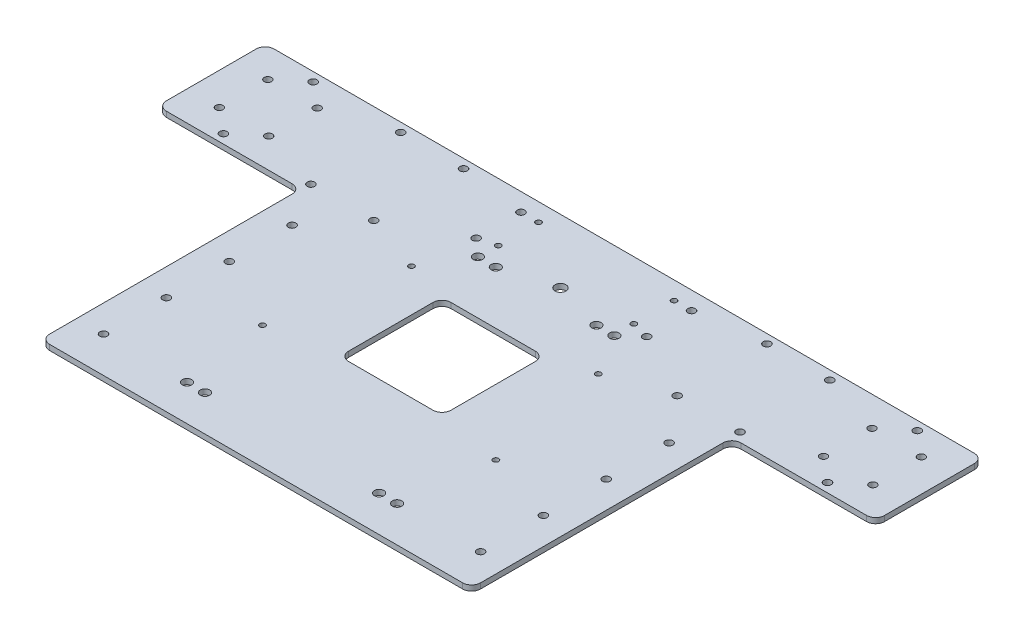
SolidWorks part; units mm, degrees
material "Thornel Mat VMA"
ref_plane "前视基准面" through (0, 0, 0) normal (0, 0, 1) x (1, 0, 0)
ref_plane "上视基准面" through (0, 0, 0) normal (0, 1, 0) x (1, 0, 0)
ref_plane "右视基准面" through (0, 0, 0) normal (1, 0, 0) x (0, 0, -1)
sketch "草图1" plane through (0, 0, 0) normal (0, 1, 0) x (1, 0, 0)
  line L0 (35.5759, -158.8718) -> (35.5759, 46.1282) construction
  line L1 (-164.4241, -13.8718) -> (235.5759, -13.8718)
  line L2 (-164.4241, -13.8718) -> (-164.4241, 46.1282)
  line L3 (-164.4241, 46.1282) -> (235.5759, 46.1282)
  line L4 (235.5759, -13.8718) -> (235.5759, 46.1282)
  line L5 (-11.9241, 36.1282) -> (83.0759, 36.1282) construction
  line L6 (-11.9241, 11.1282) -> (83.0759, 11.1282) construction
  line L7 (-84.4241, -158.8718) -> (155.5759, -158.8718)
  line L8 (-84.4241, -158.8718) -> (-84.4241, -13.8718)
  line L9 (-84.4241, -13.8718) -> (155.5759, -13.8718)
  line L10 (155.5759, -158.8718) -> (155.5759, -13.8718)
  line L11 (25.0759, 10.6282) -> (46.0759, 10.6282) construction
  line L12 (25.0759, 0.1282) -> (46.0759, 0.1282) construction
  line L13 (25.0759, 0.1282) -> (25.0759, 21.1282) construction
  line L14 (25.0759, 21.1282) -> (46.0759, 21.1282) construction
  line L15 (46.0759, 0.1282) -> (46.0759, 21.1282) construction
  line L16 (7.0759, -55.3718) -> (64.0759, -55.3718) construction
  line L17 (7.0759, -26.8718) -> (64.0759, -26.8718)
  line L18 (7.0759, -26.8718) -> (7.0759, -83.8718)
  line L19 (7.0759, -83.8718) -> (64.0759, -83.8718)
  line L20 (64.0759, -26.8718) -> (64.0759, -83.8718)
  line L21 (35.5759, 21.1282) -> (35.5759, 0.1282) construction
  circle A0 centre (-11.9241, 36.1282) radius 2.1
  circle A1 centre (-11.9241, 11.1282) radius 2.1
  circle A2 centre (83.0759, 11.1282) radius 2.1
  circle A3 centre (83.0759, 36.1282) radius 2.1
  circle A8 centre (35.5759, 10.6282) radius 3.05
  point P0 (0, 0)
  point P6 (0, -121.2547)
  point P16 (35.5759, 36.1282)
  point P19 (35.5759, 11.1282)
  point P23 (35.5759, 5.0732)
  point P30 (35.5759, -28.1434)
  point P35 (35.5759, -26.8718)
  dimension "D8" = 21
  dimension "D13" = 6.1
  dimension "D14" = 10.5
  dimension "D15" = 4.2
  dimension "D1" = 400
  dimension "D2" = 60
  dimension "D3" = 145
  dimension "D4" = 240
  dimension "D5" = 10
  dimension "D6" = 95
  dimension "D7" = 25
  dimension "D9" = 189.5
  dimension "D10" = 27
  dimension "D11" = 15
  dimension "D12" = 57
extrude "构型与裁判孔" add sketch "草图1" along normal blind 3 contours L1 L4 L3 L2 A3 L15 L12 L13 L14 A0 A1 A2 | L7 L10 L1 L8 region at (35.5759, 0, -16.1176) region at (35.5759, 0, 89.564)
sketch "草图2" plane through (0, 3, 0) normal (0, 1, 0) x (1, 0, 0)
  line L0 (-164.4241, 16.1282) -> (235.5759, 16.1282) construction
  line L1 (-164.4241, -13.8718) -> (-164.4241, 46.1282) construction
  line L2 (235.5759, -13.8718) -> (235.5759, 46.1282) construction
  line L3 (35.5759, 46.1282) -> (35.5759, -158.8718) construction
  line L4 (-164.4241, 46.1282) -> (235.5759, 46.1282) construction
  line L5 (-84.4241, -158.8718) -> (155.5759, -158.8718) construction
  line L6 (-146.4241, 2.6282) -> (-146.4241, 29.6282) construction
  line L7 (-118.9241, 2.6282) -> (-118.9241, 29.6282) construction
  line L8 (-146.4241, 29.6282) -> (-118.9241, 29.6282) construction
  line L9 (-48.9241, -8.8718) -> (-48.9241, 41.1282) construction
  line L10 (-132.6741, 29.6282) -> (-132.6741, 46.1282) construction
  line L11 (-132.6741, 41.1282) -> (-83.9241, 41.1282) construction
  circle A0 centre (-146.4241, 29.6282) radius 2.05
  circle A1 centre (-146.4241, 2.6282) radius 2.05
  circle A2 centre (-118.9241, 29.6282) radius 2.05
  circle A3 centre (-118.9241, 2.6282) radius 2.05
  circle A4 centre (-48.9241, 41.1282) radius 2.1
  circle A5 centre (-83.9241, 41.1282) radius 2.1
  circle A6 centre (-48.9241, -8.8718) radius 2.1
  circle A7 centre (-83.9241, -8.8718) radius 2.1
  circle A8 centre (-132.6741, 41.1282) radius 2.1
  circle A9 centre (-132.6741, -8.8718) radius 2.1
  circle A10 centre (203.8259, -8.8718) radius 2.1
  circle A11 centre (203.8259, 41.1282) radius 2.1
  circle A12 centre (155.0759, -8.8718) radius 2.1
  circle A13 centre (120.0759, -8.8718) radius 2.1
  circle A14 centre (155.0759, 41.1282) radius 2.1
  circle A15 centre (120.0759, 41.1282) radius 2.1
  circle A16 centre (190.0759, 2.6282) radius 2.05
  circle A17 centre (190.0759, 29.6282) radius 2.05
  circle A18 centre (217.5759, 2.6282) radius 2.05
  circle A19 centre (217.5759, 29.6282) radius 2.05
  point P15 (-146.4241, 16.1282)
  point P20 (-118.9241, 16.1282)
  point P25 (-48.9241, 16.1282)
  dimension "D2" = 4.1
  dimension "D4" = 5
  dimension "D5" = 4.2
  dimension "D7" = 2
  dimension "D8" = 18
  dimension "D1" = 27
  dimension "D3" = 45.5
  dimension "D6" = 70
extrude "切除-拉伸1" cut sketch "草图2" against normal through all
fillet "圆角1" radius 5 12 edges at (155.5759, 1.5, 13.8718) (-84.4241, 1.5, 13.8718) (235.5759, 1.5, -46.1282) (235.5759, 1.5, 13.8718) (155.5759, 1.5, 158.8718) (-84.4241, 1.5, 158.8718) (-164.4241, 1.5, -46.1282) (-164.4241, 1.5, 13.8718) (7.0759, 1.5, 83.8718) (64.0759, 1.5, 83.8718) (64.0759, 1.5, 26.8718) (7.0759, 1.5, 26.8718)
sketch "草图3" plane through (0, 3, 0) normal (0, 1, 0) x (1, 0, 0)
  line L0 (-89.4241, -13.8718) -> (160.5759, -13.8718) construction
  line L1 (-69.4241, -13.8718) -> (-69.4241, -158.8718) construction
  line L2 (-79.4241, -158.8718) -> (150.5759, -158.8718) construction
  line L3 (35.5759, 46.1282) -> (35.5759, -158.8718) construction
  line L4 (-159.4241, 46.1282) -> (230.5759, 46.1282) construction
  line L5 (-84.4241, -153.8718) -> (-84.4241, -18.8718) construction
  line L6 (7.0759, -55.3718) -> (64.0759, -55.3718) construction
  line L7 (190.0759, 2.6282) -> (-118.9241, 2.6282) construction
  line L8 (-16.4241, -20.3718) -> (-29.4241, -20.3718) construction
  line L9 (-48.9617, -13.8718) -> (-48.9617, -158.8718) construction
  line L10 (-79.4241, -158.8718) -> (150.5759, -158.8718) construction
  line L11 (-84.4241, -153.8718) -> (-84.4241, -18.8718) construction
  line L12 (-16.4241, -20.3718) -> (-16.4241, -90.3718) construction
  line L13 (-16.4241, -90.3718) -> (-29.4241, -90.3718) construction
  line L14 (-29.4241, -20.3718) -> (-29.4241, -90.3718) construction
  line L15 (-22.9241, -90.3718) -> (-22.9241, -20.3718) construction
  line L16 (-16.4241, -55.3718) -> (-29.4241, -55.3718) construction
  line L17 (7.0759, -31.8718) -> (7.0759, -78.8718) construction
  line L18 (-69.4241, -138.8718) -> (140.5759, -138.8718) construction
  circle A0 centre (-69.4241, -33.8718) radius 2.1
  circle A1 centre (-69.4241, -68.8718) radius 2.1
  circle A2 centre (-69.4241, -103.8718) radius 2.1
  circle A3 centre (-69.4241, -138.8718) radius 2.1
  circle A4 centre (140.5759, -138.8718) radius 2.1
  circle A5 centre (140.5759, -103.8718) radius 2.1
  circle A6 centre (140.5759, -68.8718) radius 2.1
  circle A7 centre (140.5759, -33.8718) radius 2.1
  circle A8 centre (-16.4241, -20.3718) radius 1.55
  circle A9 centre (-29.4241, -90.3718) radius 1.55
  circle A10 centre (100.5759, -90.3718) radius 1.55
  circle A11 centre (87.5759, -20.3718) radius 1.55
  circle A12 centre (-2.4241, 2.6282) radius 2.6
  circle A13 centre (7.5759, 2.6282) radius 2.6
  circle A14 centre (63.5759, 2.6282) radius 2.6
  circle A15 centre (73.5759, 2.6282) radius 2.6
  circle A16 centre (-22.9241, -138.8718) radius 2.6
  circle A17 centre (-12.9241, -138.8718) radius 2.6
  circle A18 centre (84.0759, -138.8718) radius 2.6
  circle A19 centre (94.0759, -138.8718) radius 2.6
  point P44 (7.0759, -55.3718)
  point P495 (-22.9241, -55.3718)
  dimension "D1" = 20
  dimension "D2" = 35
  dimension "D3" = 35
  dimension "D4" = 35
  dimension "D7" = 3.1
  dimension "D10" = 5.2
  dimension "D11" = 10
  dimension "D12" = 28
  dimension "D14" = 10
  dimension "D5" = 15
  dimension "D6" = 35.4624
  dimension "D8" = 13
  dimension "D9" = 70
  dimension "D13" = 20
  dimension "D15" = 40
extrude "切除-拉伸2" cut sketch "草图3" against normal through all
sketch "草图4" plane through (0, 3, 0) normal (0, 1, 0) x (1, 0, 0)
  line L0 (35.5759, -26.8718) -> (35.5759, 119.4643) construction
  line L1 (12.0759, -26.8718) -> (59.0759, -26.8718) construction
  line L2 (-2.1741, 36.1282) -> (73.3259, 36.1282)
  line L3 (-159.4241, 46.1282) -> (230.5759, 46.1282) construction
  line L4 (-2.1741, 36.1282) -> (-2.1741, 13.7282) construction
  circle A0 centre (-2.1741, 36.1282) radius 1.55
  circle A1 centre (73.3259, 36.1282) radius 1.55
  circle A2 centre (-2.1741, 13.7282) radius 1.55
  circle A3 centre (73.3259, 13.7282) radius 1.55
  point P7 (35.5759, 36.1282)
  dimension "D3" = 3.1
  dimension "D4" = 3.1
  dimension "D6" = 3.1
  dimension "D1" = 75.5
  dimension "D2" = 10
  dimension "D5" = 22.4
extrude "切除-拉伸3" cut sketch "草图4" against normal blind 10 contours A0 | A2 | A1 | A3
